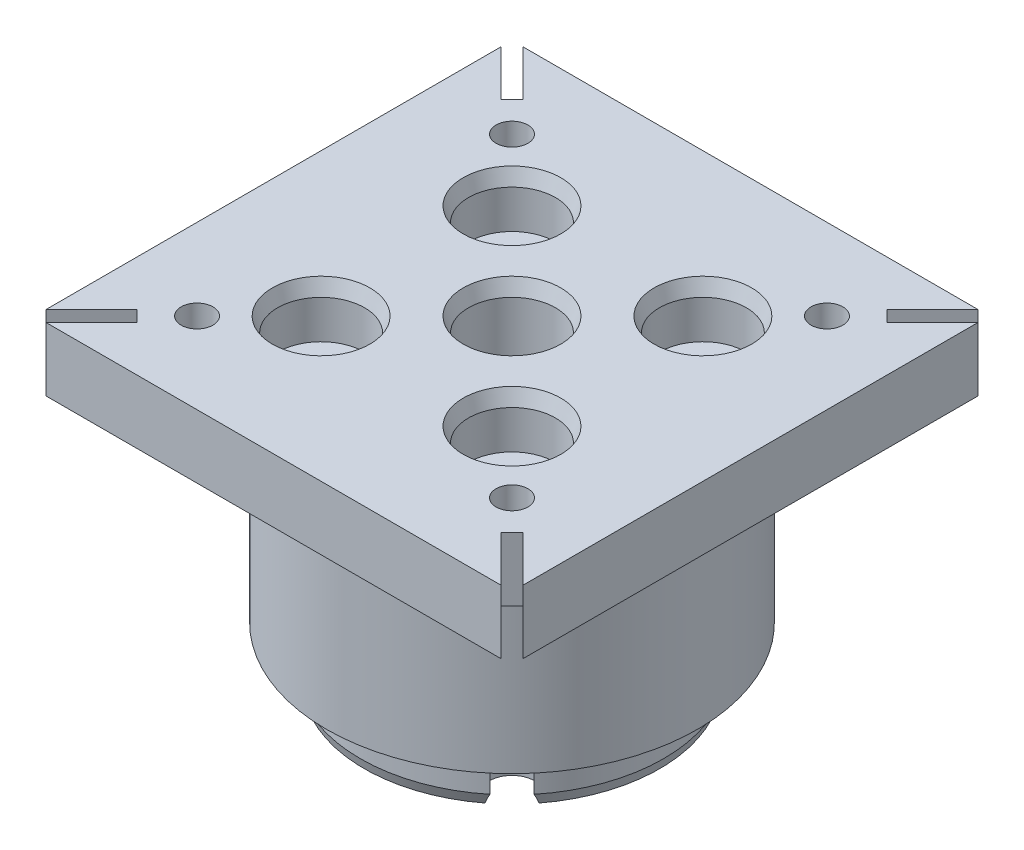
SolidWorks part; units mm, degrees
ref_plane "Спереди" through (0, 0, 0) normal (0, 0, 1) x (1, 0, 0)
ref_plane "Сверху" through (0, 0, 0) normal (0, 1, 0) x (1, 0, 0)
ref_plane "Справа" through (0, 0, 0) normal (1, 0, 0) x (0, 0, -1)
sketch "Sketch1" plane through (0, 0, 0) normal (0, 1, 0) x (1, 0, 0)
  circle A0 centre (0, 0) radius 17.5
  dimension "D1" = 35
extrude "Boss-Extrude1" add sketch "Sketch1" along normal blind 25
sketch "Sketch3" plane through (0, 0, 0) normal (0, -1, 0) x (1, 0, 0)
  circle A0 centre (0, 0) radius 14.3
  circle A1 centre (0, 0) radius 17.5 construction
  dimension "D1" = 3.2
extrude "Boss-Extrude2" add sketch "Sketch3" along normal blind 5
sketch "Sketch4" plane through (0, 25, 0) normal (0, 1, 0) x (1, 0, 0)
  line L1 (-5.2, 5.2) -> (5.2, 5.2) construction
  line L2 (-5.2, 5.2) -> (-5.2, -5.2) construction
  line L3 (-5.2, -5.2) -> (5.2, -5.2) construction
  line L4 (5.2, 5.2) -> (5.2, -5.2) construction
  line L5 (-5.2, 5.2) -> (5.2, -5.2) construction
  line L6 (-5.2, -5.2) -> (5.2, 5.2) construction
  circle A0 centre (0, 0) radius 4.1
  point P0 (0, 0)
  dimension "D2" = 8.2
  dimension "D1" = 10.4
extrude "Cut-Extrude1" cut sketch "Sketch4" against normal through all
sketch "Sketch6" plane through (0, 25, 0) normal (0, 1, 0) x (1, 0, 0)
  line L1 (-9, 9) -> (9, 9) construction
  line L2 (-9, 9) -> (-9, -9) construction
  line L3 (-9, -9) -> (9, -9) construction
  line L4 (9, 9) -> (9, -9) construction
  line L5 (-9, 9) -> (9, -9) construction
  line L6 (-9, -9) -> (9, 9) construction
  circle A0 centre (9, -9) radius 2.1
  circle A1 centre (-9, -9) radius 2.1
  circle A2 centre (-9, 9) radius 2.1
  circle A3 centre (9, 9) radius 2.1
  point P0 (0, 0)
  dimension "D1" = 4.2
  dimension "D2" = 18
extrude "Cut-Extrude2" cut sketch "Sketch6" against normal through all
chamfer "Chamfer1" distance 1 angle 20 4 edges at (14.3, -5, 0) (0, -5, -14.3) (-14.3, -5, 0) (0, -5, 14.3) first distance on face at (12.7, -2.5, 0) first distance on face at (0, -2.5, -12.7) first distance on face at (-12.7, -2.5, 0) first distance on face at (0, -2.5, 12.7)
sketch "Sketch7" plane through (0, 25, 0) normal (0, 1, 0) x (1, 0, 0)
  circle A0 centre (9, 9) radius 4.1
  circle A1 centre (-9, 9) radius 4.1
  circle A2 centre (-9, -9) radius 4.1
  circle A3 centre (9, -9) radius 4.1
  dimension "D1" = 8.2
extrude "Cut-Extrude3" cut sketch "Sketch7" against normal blind 5
chamfer "Chamfer2" distance 0.5 angle 70 1 edges at (0, 25, 4.1) first distance on face at (-9, 25, -4.9)
sketch "Sketch8" plane through (0, 25, 0) normal (0, 1, 0) x (1, 0, 0)
  line L1 (22.5, 22.5) -> (-22.5, 22.5)
  line L2 (22.5, 22.5) -> (22.5, -22.5)
  line L3 (22.5, -22.5) -> (-22.5, -22.5)
  line L4 (-22.5, 22.5) -> (-22.5, -22.5)
  line L5 (22.5, 22.5) -> (-22.5, -22.5) construction
  line L6 (22.5, -22.5) -> (-22.5, 22.5) construction
  circle A0 centre (0, 0) radius 17.5
  circle A1 centre (0, 0) radius 17.5 construction
  circle A2 centre (-14.8492, -14.8492) radius 1.5
  circle A3 centre (-14.8492, 14.8492) radius 1.5
  circle A4 centre (14.8492, 14.8492) radius 1.5
  circle A5 centre (14.8492, -14.8492) radius 1.5
  circle A6 centre (0, 0) radius 21 construction
  circle M12 centre (0, 0) radius 17.5
  dimension "D1" = 3
  dimension "D2" = 42
  dimension "D3" = 45
extrude "Boss-Extrude3" add sketch "Sketch8" against normal blind 6 contours L4 L3 A2 M12 | L3 L2 A5 M12 | L2 L1 A4 M12 | L1 L4 A3 M12 region at (21.8636, 25, 0)
sketch "Sketch10" plane through (0, 25, 0) normal (0, 1, 0) x (1, 0, 0)
  line L0 (-22.5, -22.5) -> (22.5, 22.5) construction
  line L1 (-22.5, 22.5) -> (22.5, -22.5) construction
  line L2 (-18.208, -17.1473) -> (-17.1473, -18.208)
  line L3 (-17.1473, -18.208) -> (-21.4393, -22.5)
  line L4 (22.5, -22.5) -> (-22.5, -22.5) construction
  line L5 (-21.4393, -22.5) -> (-22.5, -22.5)
  line L6 (-22.5, -22.5) -> (-22.5, -21.4393)
  line L7 (-22.5, -21.4393) -> (-18.208, -17.1473)
  line L8 (-22.5, 21.4393) -> (-18.208, 17.1473)
  line L9 (-22.5, 22.5) -> (-22.5, -22.5) construction
  line L10 (-18.208, 17.1473) -> (-17.1473, 18.208)
  line L11 (-17.1473, 18.208) -> (-21.4393, 22.5)
  line L12 (22.5, 22.5) -> (-22.5, 22.5) construction
  line L13 (-21.4393, 22.5) -> (-22.5, 22.5)
  line L14 (-22.5, 22.5) -> (-22.5, 21.4393)
  line L15 (21.4393, 22.5) -> (17.1473, 18.208)
  line L16 (17.1473, 18.208) -> (18.208, 17.1473)
  line L17 (18.208, 17.1473) -> (22.5, 21.4393)
  line L18 (22.5, 22.5) -> (22.5, -22.5) construction
  line L19 (22.5, 21.4393) -> (22.5, 22.5)
  line L20 (22.5, 22.5) -> (21.4393, 22.5)
  line L21 (17.1473, -18.208) -> (18.208, -17.1473)
  line L22 (18.208, -17.1473) -> (22.5, -21.4393)
  line L23 (22.5, -21.4393) -> (22.5, -22.5)
  line L24 (22.5, -22.5) -> (21.4393, -22.5)
  line L25 (21.4393, -22.5) -> (17.1473, -18.208)
  circle A0 centre (-14.8492, -14.8492) radius 1.5 construction
  point P10 (-17.6777, -17.6777)
  point P19 (-17.6777, 17.6777)
  point P26 (17.6777, 17.6777)
  point P33 (17.6777, -17.6777)
  dimension "D1" = 4
  dimension "D2" = 1.5
extrude "Cut-Extrude4" cut sketch "Sketch10" against normal through all
chamfer "Chamfer3" distance 0.5 angle 70 4 edges at (9, 25, -4.9) (-9, 25, -4.9) (-9, 25, 13.1) (9, 25, 13.1) first distance on face at (0, 25, 0)
sketch "Sketch11" plane through (0, -5, 0) normal (0, -1, 0) x (1, 0, 0)
  line L0 (21.4393, 22.5) -> (-21.4393, 22.5) construction
  line L1 (-3.75, 6.4952) -> (-7.5, 0)
  line L2 (-7.5, 0) -> (-3.75, -6.4952)
  line L3 (-3.75, -6.4952) -> (3.75, -6.4952)
  line L4 (3.75, -6.4952) -> (7.5, 0)
  line L5 (7.5, 0) -> (3.75, 6.4952)
  line L6 (3.75, 6.4952) -> (-3.75, 6.4952)
  circle A0 centre (0, 0) radius 7.5 construction
  dimension "D1" = 15
extrude "Cut-Extrude5" cut sketch "Sketch11" against normal blind 6.5
chamfer "Chamfer4" distance 1 angle 45 6 edges at (-5.625, -5, 3.2476) (-5.625, -5, -3.2476) (0, -5, -6.4952) (5.625, -5, -3.2476) (5.625, -5, 3.2476) (0, -5, 6.4952)
